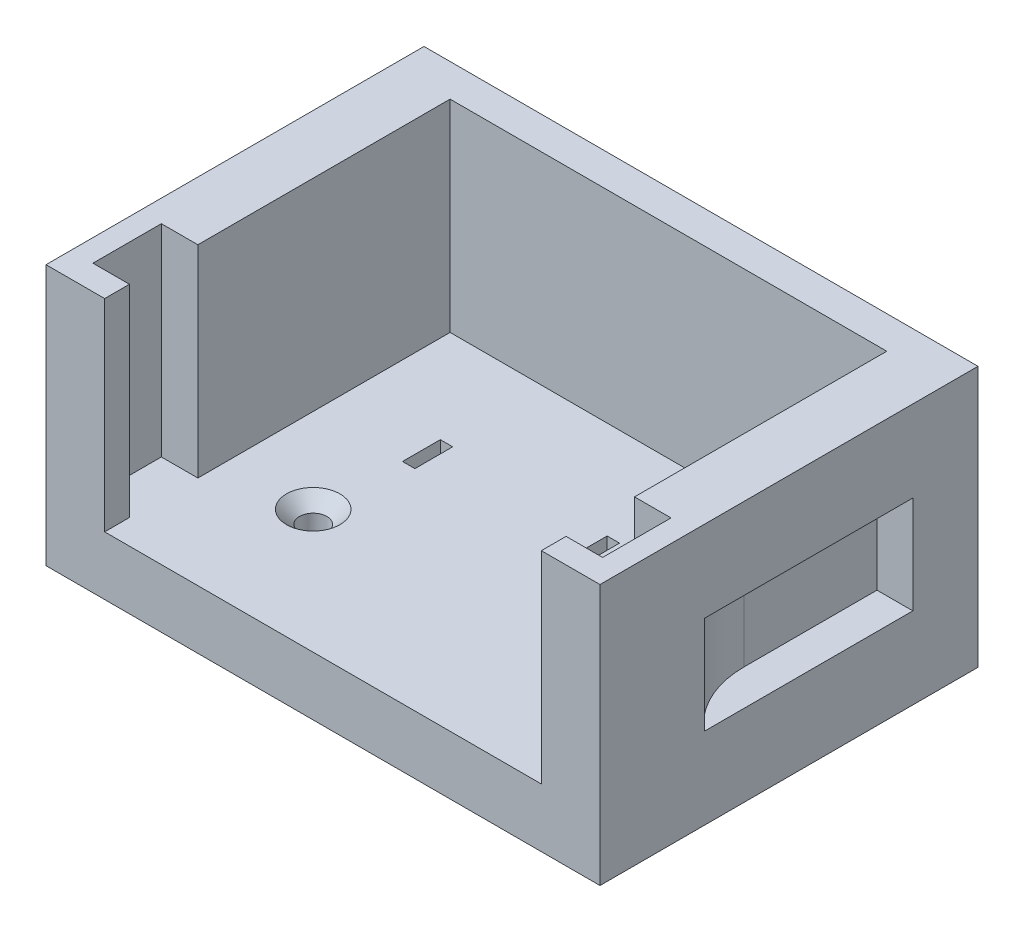
SolidWorks part; units mm, degrees
ref_plane "Front Plane" through (0, 0, 0) normal (0, 0, 1) x (1, 0, 0)
ref_plane "Top Plane" through (0, 0, 0) normal (0, 1, 0) x (1, 0, 0)
ref_plane "Right Plane" through (0, 0, 0) normal (1, 0, 0) x (0, 0, -1)
sketch "Sketch1" plane through (0, 0, 0) normal (0, 1, 0) x (1, 0, 0)
  line L1 (45.5, -35) -> (-45.5, -35)
  line L2 (45.5, -35) -> (45.5, 35)
  line L3 (45.5, 35) -> (-45.5, 35)
  line L4 (-45.5, -35) -> (-45.5, 35)
  line L5 (45.5, -35) -> (-45.5, 35) construction
  line L6 (45.5, 35) -> (-45.5, -35) construction
  point P0 (0, 0)
  dimension "D1" = 70
  dimension "D2" = 91
extrude "Boss-Extrude1" add sketch "Sketch1" along normal blind 9
sketch "Sketch2" plane through (0, 9, 0) normal (0, 1, 0) x (1, 0, 0)
  line L0 (-33.5, -35) -> (-33.5, 28)
  line L1 (-33.5, 28) -> (33.5, 28)
  line L2 (33.5, 28) -> (33.5, -35)
  line L3 (33.5, -35) -> (45.5, -35)
  line L4 (-45.5, 35) -> (-45.5, -35)
  line L5 (-45.5, -35) -> (45.5, -35)
  line L6 (45.5, -35) -> (45.5, 35)
  line L7 (45.5, 35) -> (-45.5, 35)
  line L8 (-45.5, 35) -> (-45.5, -35)
  line L9 (-45.5, -35) -> (-33.5, -35)
  line L10 (45.5, -35) -> (45.5, 35)
  line L11 (45.5, 35) -> (-45.5, 35)
  dimension "D2" = 12
  dimension "D3" = 12
  dimension "D4" = 7
  dimension "D1" = 0
extrude "Boss-Extrude2" add sketch "Sketch2" along normal blind 31
sketch "Sketch3" plane through (0, 40, 0) normal (0, 1, 0) x (1, 0, 0)
  line L0 (-33.5, -35) -> (-33.5, 28) construction
  line L1 (-33.5, -10.7) -> (-39.1, -10.7)
  line L2 (-33.5, -10.7) -> (-33.5, -21.2)
  line L3 (-33.5, -21.2) -> (-39.1, -21.2)
  line L4 (-39.1, -10.7) -> (-39.1, -21.2)
  line L5 (0, 0) -> (0, -35) construction
  line L6 (-33.5, -35) -> (33.5, -35) construction
  line L7 (33.5, -21.2) -> (39.1, -21.2)
  line L8 (39.1, -10.7) -> (39.1, -21.2)
  line L9 (33.5, -10.7) -> (39.1, -10.7)
  line L10 (33.5, -10.7) -> (33.5, -21.2)
  line L11 (-45.5, -35) -> (-33.5, -35) construction
  dimension "D1" = 5.6
  dimension "D2" = 10.5
  dimension "D3" = 13.8
extrude "Cut-Extrude1" cut sketch "Sketch3" against normal up to surface (31 mm away) up to face at (0, 9, 3.5)
sketch "Sketch4" plane through (0, 9, 0) normal (0, 1, 0) x (1, 0, 0)
  line L0 (-33.5, 28) -> (33.5, 28) construction
  line L1 (-9.5, 28) -> (-4.8, 28)
  line L2 (-9.5, 28) -> (-9.5, 23.1)
  line L3 (-9.5, 23.1) -> (-4.8, 23.1)
  line L4 (-4.8, 28) -> (-4.8, 23.1)
  line L5 (-33.5, -10.7) -> (-33.5, 28) construction
  line L6 (4.8, 28) -> (9.5, 28)
  line L7 (4.8, 28) -> (4.8, 23.1)
  line L8 (4.8, 23.1) -> (9.5, 23.1)
  line L9 (9.5, 28) -> (9.5, 23.1)
  line L10 (33.5, 28) -> (33.5, -10.7) construction
  dimension "D1" = 4.9
  dimension "D2" = 4.7
  dimension "D3" = 4.9
  dimension "D4" = 4.7
  dimension "D5" = 24
  dimension "D6" = 24
extrude "Boss-Extrude3" add sketch "Sketch4" along normal blind 18.5
fillet "Fillet1" radius 2 4 edges at (9.5, 27.5, -25.55) (4.8, 27.5, -25.55) (-4.8, 27.5, -25.55) (-9.5, 27.5, -25.55)
sketch "Sketch5" plane through (0, 9, 0) normal (0, 1, 0) x (1, 0, 0)
  line L0 (-33.5, -10.7) -> (-33.5, 28) construction
  line L1 (-20, 13) -> (-18.1, 13)
  line L2 (-20, 13) -> (-20, 7.2)
  line L3 (-20, 7.2) -> (-18.1, 7.2)
  line L4 (-18.1, 13) -> (-18.1, 7.2)
  line L5 (5.6, 13) -> (7.5, 13)
  line L6 (5.6, 13) -> (5.6, 7.2)
  line L7 (5.6, 7.2) -> (7.5, 7.2)
  line L8 (7.5, 13) -> (7.5, 7.2)
  line L9 (-33.5, 28) -> (-9.5, 28) construction
  line L10 (33.5, 28) -> (33.5, -10.7) construction
  dimension "D1" = 5.8
  dimension "D2" = 5.8
  dimension "D3" = 1.9
  dimension "D4" = 1.9
  dimension "D5" = 13.5
  dimension "D6" = 15
  dimension "D7" = 26
extrude "Cut-Extrude2" cut sketch "Sketch5" against normal blind 19
sketch "M3_bolts" plane through (0, 9, 0) normal (0, 1, 0) x (1, 0, 0)
  line L2 (33.5, -35) -> (45.5, -35) construction
  line L3 (-45.5, 35) -> (-45.5, -35) construction
  line L4 (45.5, -35) -> (45.5, 35) construction
  point P0 (-20.5, -6)
  point P1 (20.5, -6)
  dimension "D1" = 25
  dimension "D2" = 25
  dimension "D3" = 29
hole_wizard "CSK for M3.5 Flat Head Machine Screw1" positions "3DSketch1" profile "Sketch8" countersink size "M3.5" standard "ANSI Metric" end condition through all
sketch3d "3DSketch1"
  point P0 (-20.5, 9, 6)
  point P3 (20.5, 9, 6)
sketch "Sketch8" plane through (-20.5, 9, 6) normal (1, 0, 0) x (0, 0, 1)
  line L0 (0, 0) -> (0, 9)
  line L1 (0, 9) -> (2.1, 9)
  line L2 (2.1, 9) -> (2.1, 2)
  line L3 (2.1, 2) -> (4.1, 0)
  line L5 (4.1, 0) -> (0, 0)
  line L6 (-2.1, 2) -> (-4.1, 0) construction
  line L11 (0, -6.35) -> (0, 107.95) construction
  dimension "Thru Hole Dia." = 4.2
  dimension "Thru Hole Depth" = 9
  dimension "Near C'Sink Dia." = 8.2
  dimension "Near C'Sink Angle" = 90
sketch "Sketch11" plane through (0, 40, 0) normal (0, 1, 0) x (1, 0, 0)
  line L0 (-45.5, 35) -> (-45.5, -35) construction
  line L1 (-42.5, 33) -> (42.5, 33)
  line L2 (-42.5, 33) -> (-42.5, -40.9831)
  line L3 (-42.5, -40.9831) -> (42.5, -40.9831)
  line L4 (42.5, 33) -> (42.5, -40.9831)
  line L5 (45.5, -35) -> (45.5, 35) construction
  line L6 (45.5, 35) -> (-45.5, 35) construction
  line L8 (-50.807, 38.2077) -> (50.4644, 38.2077)
  line L9 (-50.807, 38.2077) -> (-50.807, -44.4602)
  line L10 (-50.807, -44.4602) -> (50.4644, -44.4602)
  line L11 (50.4644, 38.2077) -> (50.4644, -44.4602)
  dimension "D1" = 3
  dimension "D2" = 3
  dimension "D3" = 2
extrude "Cut-Extrude4" cut sketch "Sketch11" against normal blind 49
sketch "Sketch12" plane through (-42.5, 0, 0) normal (-1, 0, 0) x (0, 0, 1)
  line L1 (-23, 27.5) -> (9, 27.5)
  line L2 (-23, 27.5) -> (-23, 12.5)
  line L3 (-23, 12.5) -> (9, 12.5)
  line L4 (9, 27.5) -> (9, 12.5)
  line L6 (-33, 0) -> (-33, 40) construction
  line L7 (-33, 20) -> (-23, 20) construction
  point P6 (-23, 33.3007)
  dimension "D1" = 15
  dimension "D3" = 10
  dimension "D4" = 32
extrude "Cut-Extrude5" cut sketch "Sketch12" against normal blind 5.5
fillet "Fillet3" radius 15 1 edges at (-37, 20, 9)
mirror "Mirror1" about plane through (0, 0, 0) normal (1, 0, 0) of "Fillet3", "Cut-Extrude5"
sketch "Sketch13" plane through (0, 40, 0) normal (0, 1, 0) x (1, 0, 0)
  line L0 (42.5, -35) -> (42.5, 33) construction
  line L1 (-42.5, -35) -> (42.5, -35)
  line L2 (-42.5, -35) -> (-42.5, -25)
  line L3 (-42.5, -25) -> (42.5, -25)
  line L4 (42.5, -35) -> (42.5, -25)
  dimension "D1" = 10
extrude "Cut-Extrude6" cut sketch "Sketch13" against normal blind 53
sketch "Sketch14" plane through (0, 0, -28) normal (0, 0, 1) x (1, 0, 0)
  line L0 (-33.5, 40) -> (33.5, 40) construction
  line L1 (-13, 40) -> (10, 40)
  line L2 (-13, 40) -> (-13, 9)
  line L3 (-13, 9) -> (10, 9)
  line L4 (10, 40) -> (10, 9)
  line L5 (9.5, 9) -> (33.5, 9) construction
  line L6 (42.5, 0) -> (42.5, 40) construction
  line L7 (-42.5, 40) -> (-42.5, 0) construction
  dimension "D1" = 32.5
  dimension "D2" = 29.5
extrude "Cut-Extrude7" cut sketch "Sketch14" along normal blind 10
